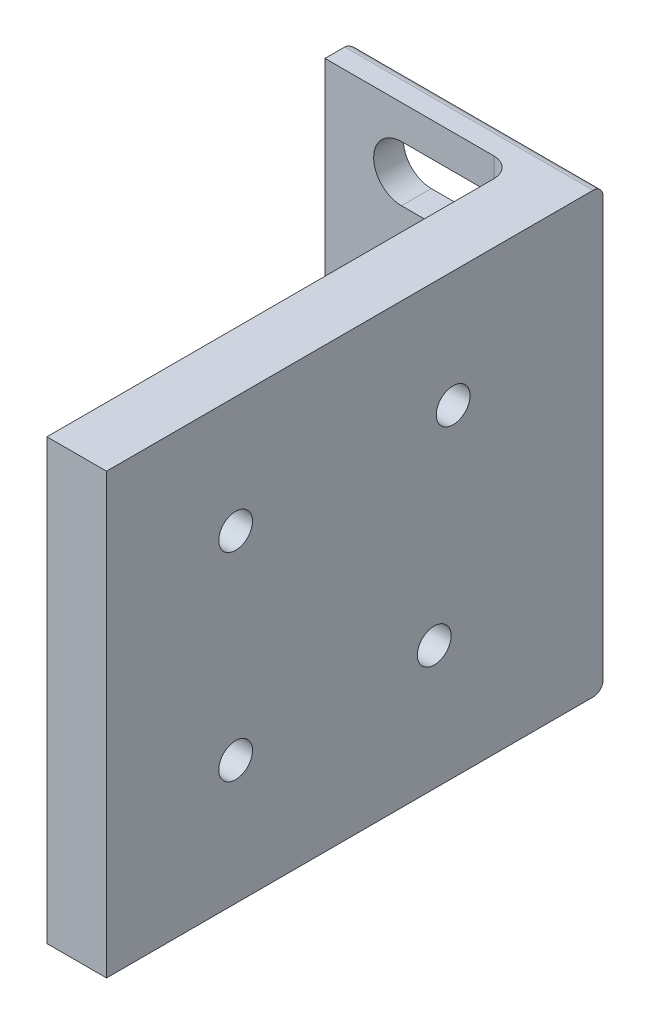
SolidWorks part; units mm, degrees
ref_plane "Front Plane" through (0, 0, 0) normal (0, 0, 1) x (1, 0, 0)
ref_plane "Top Plane" through (0, 0, 0) normal (0, 1, 0) x (1, 0, 0)
ref_plane "Right Plane" through (0, 0, 0) normal (1, 0, 0) x (0, 0, -1)
sketch "Sketch1" plane through (0, 0, 0) normal (0, 0, 1) x (1, 0, 0)
  line L1 (-12.5, 22.1) -> (12.5, 22.1)
  line L2 (-12.5, 22.1) -> (-12.5, -22.1)
  line L3 (-12.5, -22.1) -> (12.5, -22.1)
  line L4 (12.5, 22.1) -> (12.5, -22.1)
  line L5 (-12.5, 22.1) -> (12.5, -22.1) construction
  line L6 (-12.5, -22.1) -> (12.5, 22.1) construction
  point P0 (0, 0)
  dimension "D1" = 25
  dimension "D2" = 44.2
extrude "Boss-Extrude1" add sketch "Sketch1" along normal blind 3
sketch "Sketch2" plane through (0, 0, 3) normal (0, 0, 1) x (1, 0, 0)
  line L0 (-12.5, -22.1) -> (12.5, -22.1) construction
  line L1 (12.5, 22.1) -> (6.5, 22.1)
  line L2 (12.5, 22.1) -> (12.5, -22.1)
  line L3 (12.5, -22.1) -> (6.5, -22.1)
  line L4 (6.5, 22.1) -> (6.5, -22.1)
  dimension "D1" = 6
extrude "Boss-Extrude2" add sketch "Sketch2" along normal blind 47
sketch "Sketch5" plane through (6.5, 0, 0) normal (-1, 0, 0) x (0, 0, 1)
  line L0 (0, -22.1) -> (0, 22.1) construction
  line L1 (50, -22.1) -> (3, -22.1) construction
  point P0 (17, -9.6)
  point P2 (37, -9.6)
  point P4 (37, 10.4)
  point P6 (15.0937, 10.4)
  point P13 (0, 0)
  point P14 (0, 0)
  point P15 (0, 0)
  dimension "D1" = 17
  dimension "D2" = 20
  dimension "D3" = 12.5
  dimension "D4" = 20
hole_wizard "CBORE for M3 SHCS1" positions "Sketch5" profile "Sketch4" counterbore size "M3" standard "ANSI Metric"
sketch "Sketch4" plane through (6.5, -9.6, 17) normal (0, 1, 0) x (0, 0, 1)
  line L0 (0, 0) -> (0, 11.1215)
  line L1 (0, 11.1215) -> (1.7, 10.1)
  line L2 (1.7, 10.1) -> (1.7, 3)
  line L3 (1.7, 3) -> (3.25, 3)
  line L4 (3.25, 3) -> (3.25, 0)
  line L5 (3.25, 0) -> (0, 0)
  line L10 (0, 11.1215) -> (-1.7, 10.1) construction
  line L11 (0, -6.35) -> (0, 107.95) construction
  dimension "Hole Dia." = 3.4
  dimension "Hole Depth" = 10.1
  dimension "C'Bore Dia." = 6.5
  dimension "C'Bore Depth" = 3
  dimension "Drill Angle" = 118
fillet "Fillet1" radius 1 3 edges at (-12.5, 0, 0) (0, 22.1, 0) (0, -22.1, 0)
sketch "Sketch6" plane through (0, 0, 0) normal (0, 0, -1) x (-1, 0, 0)
  line L0 (-3.2, -15.9) -> (4.8, -15.9) construction
  line L1 (-3.2, -13.1) -> (4.8, -13.1)
  line L2 (-3.2, -18.7) -> (4.8, -18.7)
  line L3 (-3.2, 15.9) -> (4.8, 15.9) construction
  line L4 (-3.2, 18.7) -> (4.8, 18.7)
  line L5 (-12.5, -21.1) -> (-12.5, 21.1) construction
  line L7 (-3.2, 13.1) -> (4.8, 13.1)
  arc A0 (-3.2, -13.1) -> (-3.2, -18.7) centre (-3.2, -15.9) ccw
  arc A1 (4.8, -18.7) -> (4.8, -13.1) centre (4.8, -15.9) ccw
  arc A2 (-3.2, 18.7) -> (-3.2, 13.1) centre (-3.2, 15.9) ccw
  arc A3 (4.8, 13.1) -> (4.8, 18.7) centre (4.8, 15.9) ccw
  point P2 (0.8, -15.9)
  point P14 (0.8, 15.9)
  dimension "D2" = 8
  dimension "D3" = 6.5
  dimension "D1" = 5.6
  dimension "D4" = 15.9
  dimension "D6" = 15.9
  dimension "D5" = 2
extrude "Cut-Extrude1" cut sketch "Sketch6" against normal blind 47
fillet "Fillet2" radius 2 1 edges at (6.5, 0, 3)
